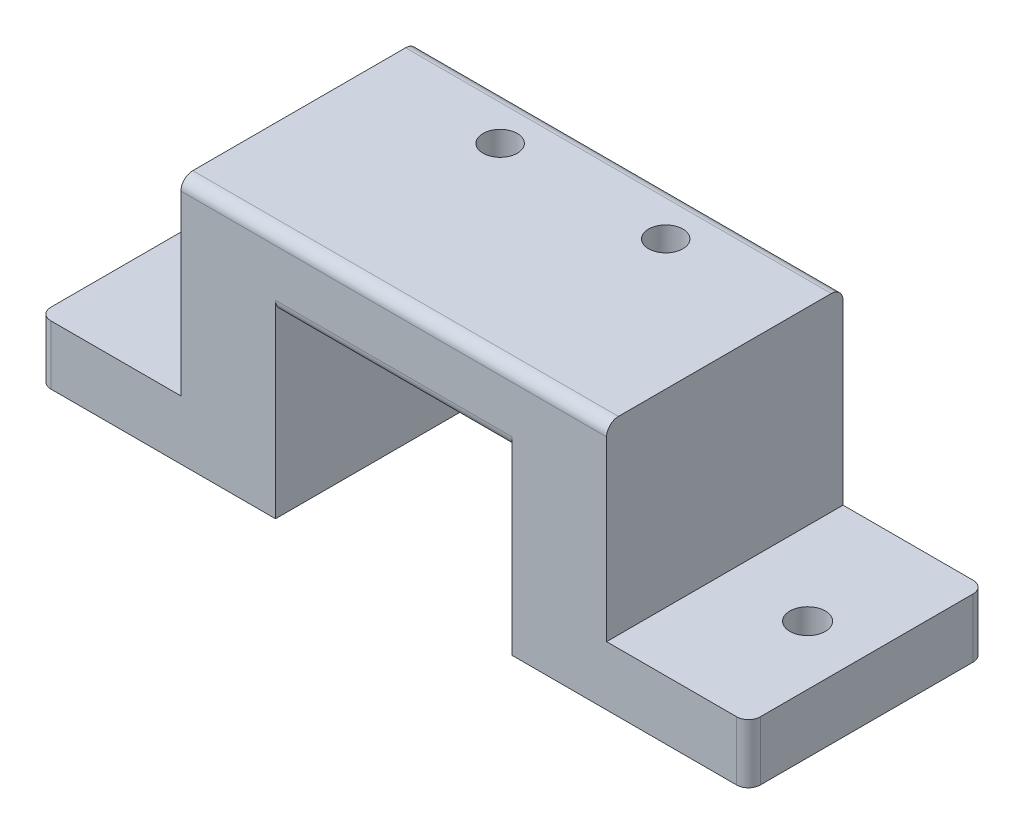
SolidWorks part; units mm, degrees
ref_plane "Front Plane" through (0, 0, 0) normal (0, 0, 1) x (1, 0, 0)
ref_plane "Top Plane" through (0, 0, 0) normal (0, 1, 0) x (1, 0, 0)
ref_plane "Right Plane" through (0, 0, 0) normal (1, 0, 0) x (0, 0, -1)
sketch "Sketch1" plane through (0, 0, 0) normal (0, 1, 0) x (1, 0, 0)
  line L1 (-27.6146, 5) -> (-7.6146, 5)
  line L2 (-27.6146, 5) -> (-27.6146, -15)
  line L3 (-27.6146, -15) -> (-7.6146, -15)
  line L4 (-7.6146, 5) -> (-7.6146, -15)
  line L5 (12.3854, 5) -> (32.3854, 5)
  line L6 (12.3854, 5) -> (12.3854, -15)
  line L7 (12.3854, -15) -> (32.3854, -15)
  line L8 (32.3854, 5) -> (32.3854, -15)
  circle A0 centre (-22.6146, -5) radius 1.5
  circle A1 centre (27.3854, -5) radius 1.5
  dimension "D7" = 3
  dimension "D1" = 20
  dimension "D2" = 20
  dimension "D3" = 20
  dimension "D4" = 10
  dimension "D5" = 5
  dimension "D6" = 5
extrude "Boss-Extrude1" add sketch "Sketch1" along normal blind 5
sketch "Sketch2" plane through (0, 5, 0) normal (0, 1, 0) x (1, 0, 0)
  line L0 (-7.6146, 5) -> (-27.6146, 5) construction
  line L1 (-15.6146, 5) -> (-7.6146, 5)
  line L2 (-15.6146, 5) -> (-15.6146, -15)
  line L3 (-15.6146, -15) -> (-7.6146, -15)
  line L4 (-7.6146, 5) -> (-7.6146, -15)
  line L5 (12.3854, -15) -> (32.3854, -15) construction
  line L6 (12.3854, -15) -> (20.3854, -15)
  line L7 (12.3854, -15) -> (12.3854, 5)
  line L8 (12.3854, 5) -> (20.3854, 5)
  line L9 (20.3854, -15) -> (20.3854, 5)
  line L10 (12.3854, 5) -> (12.3854, -15) construction
  line L11 (32.3854, 5) -> (12.3854, 5) construction
  dimension "D1" = 8
extrude "Boss-Extrude2" add sketch "Sketch2" along normal blind 10
sketch "Sketch3" plane through (-15.6146, 0, 0) normal (-1, 0, 0) x (0, 0, 1)
  line L0 (15, 15) -> (15, 5) construction
  line L1 (-5, 15) -> (15, 15)
  line L2 (-5, 15) -> (-5, 21)
  line L3 (-5, 21) -> (15, 21)
  line L4 (15, 15) -> (15, 21)
  dimension "D1" = 6
extrude "Boss-Extrude3" add sketch "Sketch3" against normal up to surface (36 mm away) contours L3 L4 L1 L2 up to face at (20.3854, 10, 5)
sketch "Sketch4" plane through (0, 15, 0) normal (0, -1, 0) x (1, 0, 0)
  line L2 (5.6354, -2.0693) -> (5.6354, -13.5488)
  line L4 (12.3854, -5) -> (-7.6146, -5) construction
  line L5 (5.6354, -13.5488) -> (-0.8646, -13.5488)
  line L6 (-0.8646, -13.5488) -> (-0.8646, -2.0693)
  arc A0 (5.6354, -2.0693) -> (6.8316, 2.5018) centre (14.967, -2.0693) cw
  arc A2 (6.8316, 2.5018) -> (-2.0608, 2.5018) centre (2.3854, 5) ccw
  arc A3 (-2.0608, 2.5018) -> (-0.8646, -2.0693) centre (-10.1962, -2.0693) cw
  point P9 (0, -1.1507)
  point P10 (0, 0)
  point P12 (0, 0)
  point P13 (0, 0)
  point P14 (6.5, -3.1731)
  point P17 (5.5042, 0.9648)
  point P18 (0, -5)
  point P19 (0, -1.2399)
  point P20 (6.2559, -1.9054)
  point P21 (6.5, -11.2263)
  point P23 (0, -15.602)
  point P24 (6.5, -3.3771)
  point P25 (5.5317, 0.9862)
  point P26 (7.0451, 2.927)
  point P27 (6.6425, 1.7169)
  point P28 (0, 0)
  point P29 (0, 0)
  point P30 (5.6733, -2.1363)
  point P31 (0, 0)
  dimension "D1" = 5.1
  dimension "D2" = 10
  dimension "D3" = 6.5
  dimension "D4" = 10
extrude "Cut-Extrude1" cut sketch "Sketch4" against normal blind 0.6
sketch "Sketch6" plane through (0, 0, -5) normal (0, 0, -1) x (-1, 0, 0)
  line L0 (-12.3854, 15) -> (-5.6354, 15) construction
  line L1 (-14.3854, 15) -> (9.7146, 15)
  line L2 (-14.3854, 15) -> (-14.3854, 13.4)
  line L3 (-14.3854, 13.4) -> (9.7146, 13.4)
  line L4 (9.7146, 15) -> (9.7146, 13.4)
  line L5 (7.6146, 15) -> (7.6146, 0) construction
  dimension "D1" = 2
  dimension "D2" = 2.1
  dimension "D3" = 1.6
extrude "Cut-Extrude2" cut sketch "Sketch6" against normal blind 17.5
fillet "Fillet1" radius 1 6 edges at (2.3854, 21, -5) (2.3854, 21, 15) (32.3854, 2.5, 15) (32.3854, 2.5, -5) (-27.6146, 2.5, 15) (-27.6146, 2.5, -5)
sketch "Sketch8" plane through (0, 15, 0) normal (0, -1, 0) x (-1, 0, 0)
  line L0 (7.6146, -15) -> (7.6146, 5) construction
  line L1 (-14.3854, 5) -> (-5.6354, 5) construction
  circle A0 centre (4.6146, 1) radius 1.45
  circle A1 centre (-9.3854, 1) radius 1.45
  dimension "D1" = 14
  dimension "D2" = 2.9
  dimension "D3" = 3
  dimension "D4" = 4
extrude "Cut-Extrude3" cut sketch "Sketch8" against normal blind 6
fillet "Fillet2" radius 1 3 edges at (2.3854, 15, 15) (10.0104, 15, -5) (-5.2896, 15, -5)
